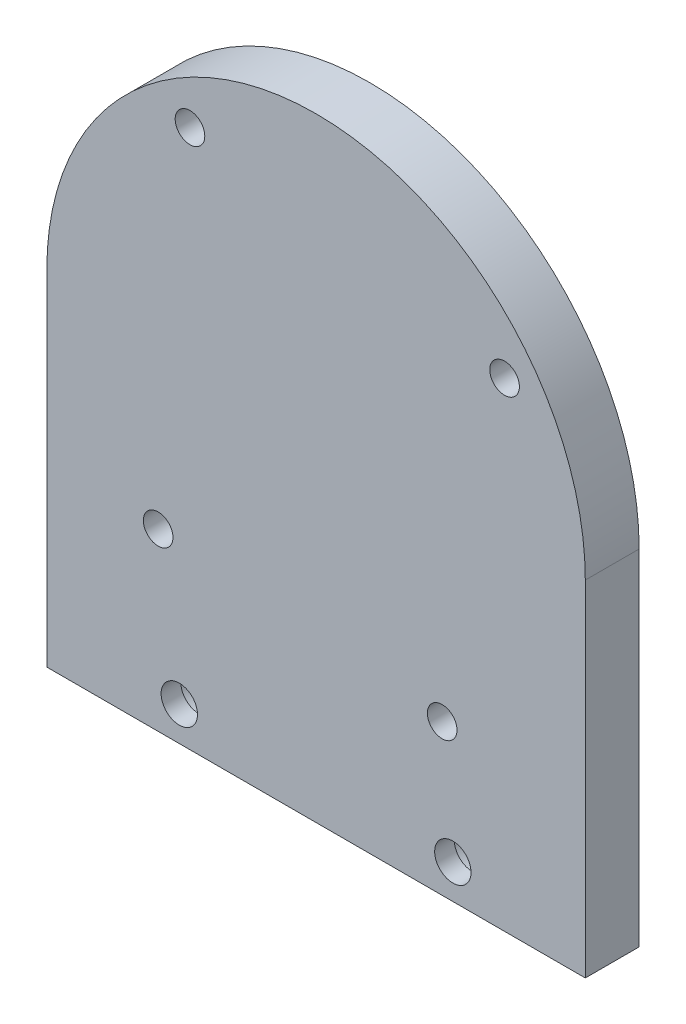
SolidWorks part; units mm, degrees
ref_plane "Front Plane" through (0, 0, 0) normal (0, 0, 1) x (1, 0, 0)
ref_plane "Top Plane" through (0, 0, 0) normal (0, 1, 0) x (1, 0, 0)
ref_plane "Right Plane" through (0, 0, 0) normal (1, 0, 0) x (0, 0, -1)
sketch "Sketch1" plane through (0, 0, 0) normal (0, 0, 1) x (1, 0, 0)
  line L1 (50, 0) -> (-50, 0)
  line L2 (50, 0) -> (50, -64)
  line L3 (50, -64) -> (-50, -64)
  line L4 (-50, 0) -> (-50, -64)
  circle A0 centre (0, 0) radius 50
  dimension "D1" = 100
  dimension "D2" = 64
extrude "Boss-Extrude1" add sketch "Sketch1" along normal blind 10 contours A0 L3 L2 | A0 L4 L3 | L1 A0 | L1 A0
ref_point "Point1"
sketch "Sketch3" plane through (0, 0, 0) normal (0, 0, -1) x (-1, 0, 0)
  line L0 (0, 43) -> (0, 0)
  line L1 (0, 0) -> (0, -43)
  circle A0 centre (0, 0) radius 43
  dimension "D1" = 86
hole_wizard "CBORE for M5 SHCS1" positions "Sketch8" profile "Sketch9" counterbore size "M5" standard "ANSI Metric" end condition up to next
sketch "Sketch8" plane through (0, 0, 0) normal (0, 0, -1) x (-1, 0, 0)
  circle A0 centre (0, 0) radius 43 construction
  point P0 (-35.007, 24.9702)
  point P7 (-23.4195, -36.0628)
  point P10 (29.3259, -31.4482)
  point P12 (23.4195, 36.0628)
  dimension "D1" = 54.5
  dimension "D2" = 33
  dimension "D3" = 33
  dimension "D4" = 43
sketch "Sketch9" plane through (35.007, 24.9702, 0) normal (1, 0, 0) x (0, 1, 0)
  line L0 (0, 0) -> (0, 10)
  line L1 (0, 10) -> (2.75, 10)
  line L3 (2.75, 10) -> (2.75, 5)
  line L4 (2.75, 5) -> (5, 5)
  line L5 (5, 5) -> (5, 0)
  line L7 (5, 0) -> (0, 0)
  line L11 (0, -6.35) -> (0, 107.95) construction
  dimension "Thru Hole Dia." = 5.5
  dimension "Thru Hole Depth" = 10
  dimension "C'Bore Dia." = 10
  dimension "C'Bore Depth" = 5
sketch "Sketch10" plane through (0, 0, 0) normal (0, 0, -1) x (-1, 0, 0)
  line L0 (0, -64) -> (0, -57.65)
  line L1 (-50, -64) -> (50, -64) construction
  line L2 (-25.4, -57.65) -> (25.4, -57.65)
  point P8 (0, -57.65)
  dimension "D1" = 50.8
  dimension "D2" = 6.35
hole_wizard "CBORE for 1/4 Socket Head Cap Screw1" positions "Sketch13" profile "Sketch14" counterbore size "1/4" standard "ANSI Inch" end condition up to next
sketch "Sketch13" plane through (0, 0, 0) normal (0, 0, -1) x (-1, 0, 0)
  point P0 (-25.4, -57.65)
  point P3 (25.4, -57.65)
sketch "Sketch14" plane through (25.4, -57.65, 0) normal (1, 0, 0) x (0, 1, 0)
  line L0 (0, 0) -> (0, 10)
  line L1 (0, 10) -> (3.3782, 10)
  line L3 (3.3782, 10) -> (3.3782, 6.35)
  line L4 (3.3782, 6.35) -> (5.5562, 6.35)
  line L5 (5.5562, 6.35) -> (5.5563, 0)
  line L7 (5.5563, 0) -> (0, 0)
  line L11 (0, -6.35) -> (0, 107.95) construction
  dimension "Thru Hole Dia." = 6.7564
  dimension "Thru Hole Depth" = 10
  dimension "C'Bore Dia." = 11.1125
  dimension "C'Bore Depth" = 6.35
sketch "Sketch15" plane through (0, -64, 0) normal (0, -1, 0) x (1, 0, 0)
  line L4 (-50, 0) -> (50, 0)
  line L5 (50, 0) -> (50, 10)
  line L6 (50, 10) -> (-50, 10)
  line L7 (-50, 10) -> (-50, 0)
  line L8 (-50, 0) -> (50, 0)
  line L9 (50, 0) -> (50, 10)
  line L10 (50, 10) -> (-50, 10)
  line L11 (-50, 10) -> (-50, 0)
  dimension "D1" = 0
ref_point "Point2"
